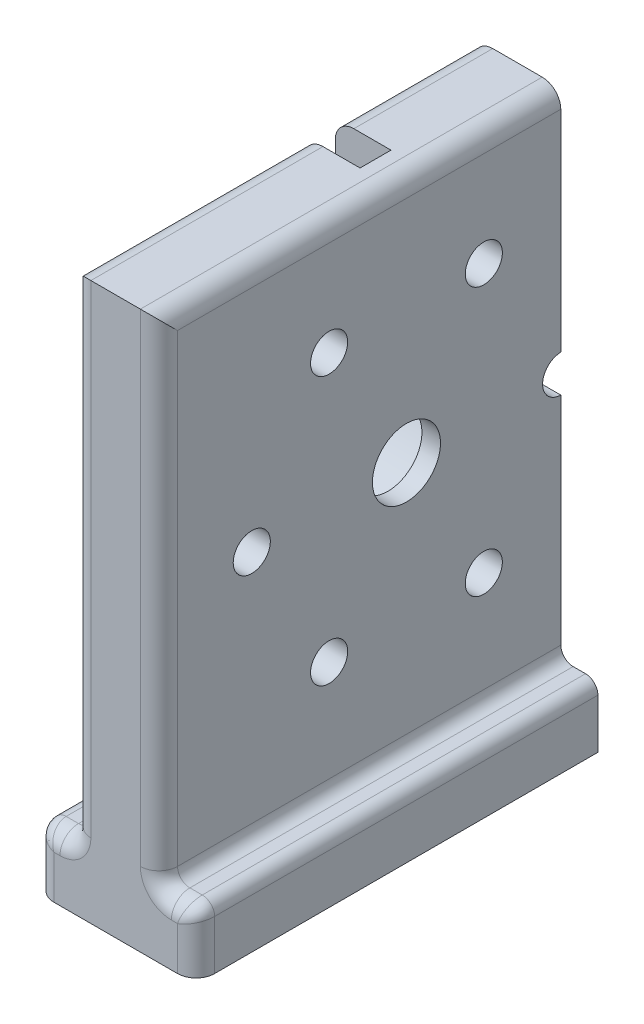
SolidWorks part; units mm, degrees
ref_plane "Front Plane" through (0, 0, 0) normal (0, 0, 1) x (1, 0, 0)
ref_plane "Top Plane" through (0, 0, 0) normal (0, 1, 0) x (1, 0, 0)
ref_plane "Right Plane" through (0, 0, 0) normal (1, 0, 0) x (0, 0, -1)
sketch "Sketch1" plane through (0, 0, 0) normal (0, 1, 0) x (1, 0, 0)
  line L1 (-3.5, 20) -> (3.5, 20)
  line L2 (-3.5, 20) -> (-3.5, -20)
  line L3 (-3.5, -20) -> (3.5, -20)
  line L4 (3.5, 20) -> (3.5, -20)
  line L5 (-3.5, 20) -> (3.5, -20) construction
  line L6 (-3.5, -20) -> (3.5, 20) construction
  point P0 (0, 0)
  dimension "D1" = 7
  dimension "D2" = 40
extrude "Boss-Extrude1" add sketch "Sketch1" along normal blind 45
sketch "Sketch3" plane through (3.5, 0, 0) normal (1, 0, 0) x (0, 0, -1)
  line L0 (-20, 45) -> (-20, 0) construction
  line L1 (20, 0) -> (-20, 0)
  line L2 (20, 0) -> (20, 5)
  line L3 (20, 5) -> (-20, 5)
  line L4 (-20, 0) -> (-20, 5)
  dimension "D1" = 5
extrude "Boss-Extrude2" add sketch "Sketch3" along normal blind 3 and the other way blind 10
sketch "Sketch4" plane through (0, 0, 0) normal (0, -1, 0) x (1, 0, 0)
  line L0 (7.15, 0) -> (-7.15, 0) construction
  circle A0 centre (0, 8) radius 1.9
  circle A1 centre (0, -8) radius 1.9
  dimension "D1" = 3.8
  dimension "D2" = 8
extrude "Cut-Extrude2" cut sketch "Sketch4" against normal blind 10
sketch "Sketch5" plane through (-3.5, 0, 0) normal (-1, 0, 0) x (0, 0, 1)
  line L0 (20, 45) -> (20, 5) construction
  line L1 (-20, 45) -> (20, 45) construction
  line L2 (20, 0) -> (-20, 0) construction
  circle A0 centre (0, 25) radius 12.5 construction
  circle A1 centre (-12.5, 25) radius 1.5
  circle A2 centre (-6.25, 35.8253) radius 1.5
  circle A3 centre (6.25, 35.8253) radius 1.5
  circle A4 centre (12.5, 25) radius 1.5
  circle A5 centre (6.25, 14.1747) radius 1.5
  circle A6 centre (-6.25, 14.1747) radius 1.5
  circle A7 centre (0, 25) radius 2.75
  dimension "D1" = 25
  dimension "D4" = 3
  dimension "D6" = 5.5
  dimension "D2" = 20
  dimension "D3" = 20
  dimension "D7" = 25
  dimension "D5" = 6
extrude "Cut-Extrude3" cut sketch "Sketch5" against normal through all
sketch "Sketch6" plane through (-3.5, 0, 0) normal (-1, 0, 0) x (0, 0, 1)
  circle A0 centre (0, 25) radius 7
  dimension "D1" = 14
extrude "Cut-Extrude4" cut sketch "Sketch6" against normal blind 5.5
fillet "Fillet1" radius 1 4 edges at (-3.5, 5, 0) (-6.5, 5, 0) (6.5, 5, 0) (3.5, 5, 0)
sketch "Sketch7" plane through (-3.5, 0, 0) normal (-1, 0, 0) x (0, 0, 1)
  line L0 (-1.25, 45) -> (-1.25, 31.8875)
  line L1 (-20, 45) -> (20, 45) construction
  line L2 (1.25, 45) -> (1.25, 31.8875)
  line L3 (-1.25, 45) -> (1.25, 45)
  circle A0 centre (0, 25) radius 7 construction
  circle A1 centre (0, 25) radius 7 construction
  arc A5 (-1.25, 31.8875) -> (1.25, 31.8875) centre (0, 25) cw
  dimension "D1" = 2.5
  dimension "D2" = 1.25
extrude "Cut-Extrude5" cut sketch "Sketch7" against normal blind 4.5
fillet "Fillet2" radius 1.5 23 edges at (6.5, 2, -20) (6.2071, 4.7071, -20) (3.7929, 5.2929, -20) (6.5, 2, 20) (6.2071, 4.7071, 20) (3.7929, 5.2929, 20) (-6.5, 2, 20) (-6.2071, 4.7071, 20) (-3.7929, 5.2929, 20) (-6.5, 2, -20) (-6.2071, 4.7071, -20) (-3.7929, 5.2929, -20) (-3.5, 45, 10.625) (3.5, 45, 0) (-3.5, 45, -10.625) (3.5, 25.5, -20) (3.5, 25.5, 20) (-3.5, 25.5, 20) (-3.5, 25.5, -20) (5, 5, -20) (5, 5, 20) (-5, 5, 20) (-5, 5, -20)
sketch "Sketch8" plane through (-3.5, 0, 0) normal (-1, 0, 0) x (0, 0, 1)
  line L0 (-12.471, 45) -> (-12.471, 0)
  line L1 (-20, 45) -> (-1.25, 45) construction
  line L2 (18.5, 0) -> (-18.5, 0) construction
  line L3 (-12.471, 0) -> (-20, 0)
  line L4 (-20, 0) -> (-20, 45)
  line L5 (-20, 45) -> (-12.471, 45)
extrude "Cut-Extrude6" cut sketch "Sketch8" against normal through all both and the other way through all
